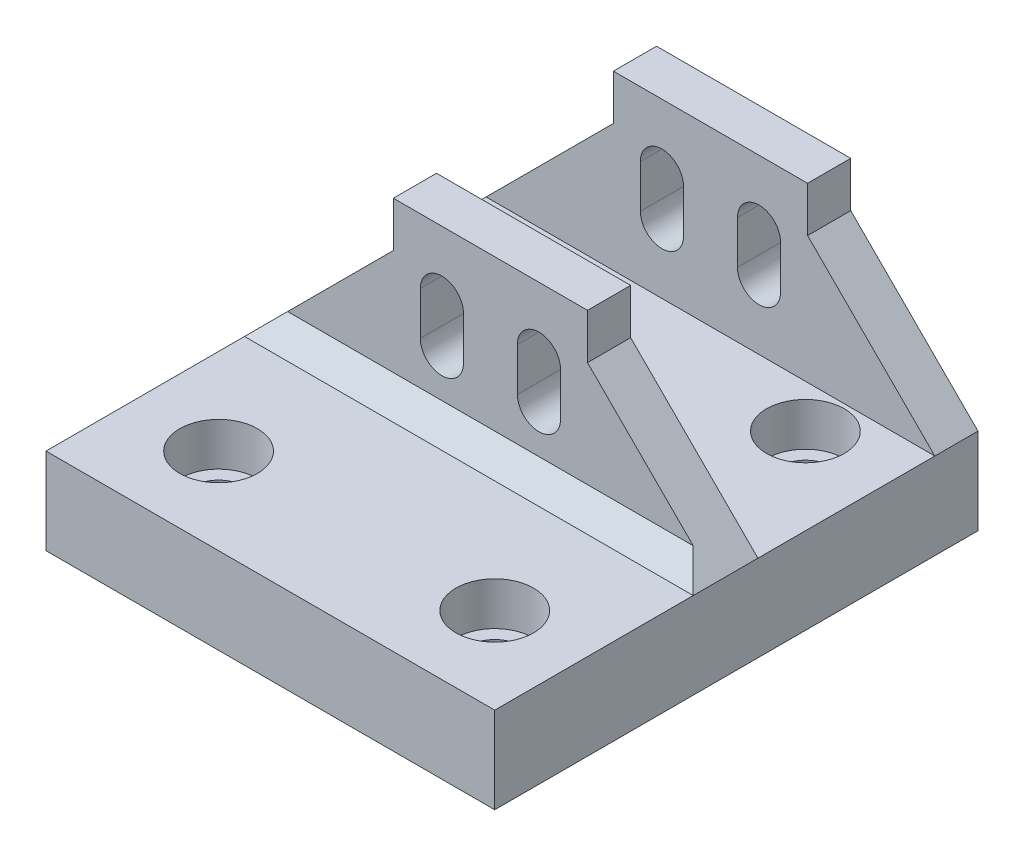
SolidWorks part; units mm, degrees
ref_plane "Front Plane" through (0, 0, 0) normal (0, 0, 1) x (1, 0, 0)
ref_plane "Top Plane" through (0, 0, 0) normal (0, 1, 0) x (1, 0, 0)
ref_plane "Right Plane" through (0, 0, 0) normal (1, 0, 0) x (0, 0, -1)
sketch "Sketch1" plane through (0, 0, 0) normal (0, 1, 0) x (1, 0, 0)
  line L0 (26, 0) -> (26, 51.7899) construction
  line L1 (0, 0) -> (52, 0)
  line L2 (0, 0) -> (0, 56)
  line L3 (0, 56) -> (52, 56)
  line L4 (52, 0) -> (52, 56)
  line L5 (10, 46) -> (42, 46) construction
  line L6 (10, 46) -> (10, 10) construction
  line L7 (10, 10) -> (42, 10) construction
  line L8 (42, 46) -> (42, 10) construction
  line L9 (54.3221, 28) -> (0, 28) construction
  circle A0 centre (10, 46) radius 2.95
  circle A1 centre (42, 46) radius 2.95
  circle A2 centre (42, 10) radius 2.95
  circle A3 centre (10, 10) radius 2.95
  dimension "D7" = 5.9
  dimension "D1" = 32
  dimension "D2" = 36
  dimension "D3" = 10
  dimension "D4" = 10
  dimension "D5" = 10
  dimension "D6" = 10
extrude "Boss-Extrude1" add sketch "Sketch1" along normal blind 10
sketch "Sketch2" plane through (0, 10, 0) normal (0, 1, 0) x (1, 0, 0)
  circle A0 centre (10, 10) radius 4.5
  circle A1 centre (42, 10) radius 4.5
  circle A2 centre (42, 46) radius 4.5
  circle A3 centre (10, 46) radius 4.5
  dimension "D1" = 9
extrude "Cut-Extrude1" cut sketch "Sketch2" against normal blind 5 and the other way through all
sketch "Sketch3" plane through (52, 0, 0) normal (1, 0, 0) x (0, 0, -1)
  line L0 (0, 10) -> (56, 10) construction
  line L1 (25.5, 10) -> (30.5, 10)
  line L2 (25.5, 10) -> (25.5, 30)
  line L3 (25.5, 30) -> (30.5, 30)
  line L4 (30.5, 10) -> (30.5, 30)
  line L5 (56, 10) -> (56, 0) construction
  line L6 (56, 10) -> (51, 10)
  line L7 (56, 10) -> (56, 30)
  line L8 (56, 30) -> (51, 30)
  line L9 (51, 10) -> (51, 30)
  dimension "D1" = 20.5
  dimension "D2" = 5
  dimension "D3" = 20
extrude "Boss-Extrude2" add sketch "Sketch3" against normal blind 22.5 from offset 14.75 offset against normal yes
sketch "Sketch4" plane through (0, 0, -25.5) normal (0, 0, 1) x (1, 0, 0)
  line L0 (20.375, 22.5) -> (20.375, 17.5) construction
  line L1 (22.875, 22.5) -> (22.875, 17.5)
  line L2 (17.875, 22.5) -> (17.875, 17.5)
  line L3 (31.625, 22.5) -> (31.625, 17.5) construction
  line L4 (34.125, 22.5) -> (34.125, 17.5)
  line L5 (29.125, 22.5) -> (29.125, 17.5)
  line L6 (14.75, 10) -> (37.25, 10) construction
  line L7 (26, 27.2126) -> (26, 33.0182) construction
  line L8 (14.75, 30) -> (37.25, 30) construction
  arc A0 (22.875, 22.5) -> (17.875, 22.5) centre (20.375, 22.5) ccw
  arc A1 (17.875, 17.5) -> (22.875, 17.5) centre (20.375, 17.5) ccw
  arc A2 (34.125, 22.5) -> (29.125, 22.5) centre (31.625, 22.5) ccw
  arc A3 (29.125, 17.5) -> (34.125, 17.5) centre (31.625, 17.5) ccw
  point P2 (20.375, 20)
  point P7 (31.625, 20)
  point P20 (26, 30)
  dimension "D1" = 5
  dimension "D2" = 5
  dimension "D3" = 10
  dimension "D4" = 5.625
extrude "Cut-Extrude2" cut sketch "Sketch4" against normal up to surface (30.5 mm away) up to face at (26, 12.5, -56)
chamfer "Chamfer1" distance 14.75 angle 45 4 edges at (37.25, 10, -53.5) (37.25, 10, -28) (14.75, 10, -53.5) (14.75, 10, -28)
chamfer "Chamfer2" distance 2.5 angle 45 1 edges at (26, 10, -25.5)
